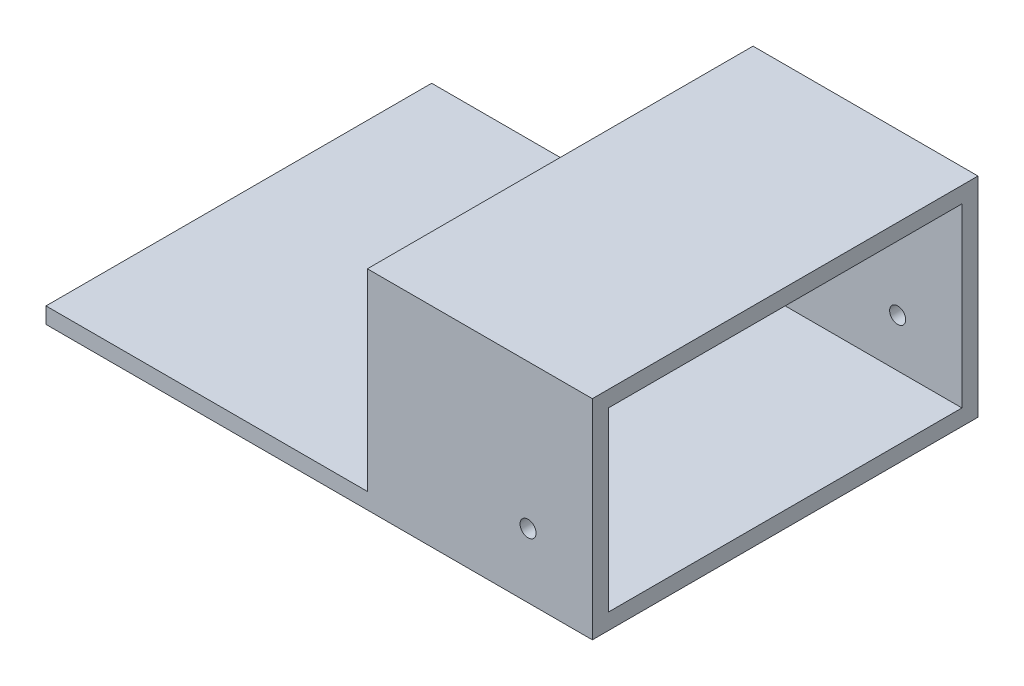
SolidWorks part; units mm, degrees
ref_plane "Front Plane" through (0, 0, 0) normal (0, 0, 1) x (1, 0, 0)
ref_plane "Top Plane" through (0, 0, 0) normal (0, 1, 0) x (1, 0, 0)
ref_plane "Right Plane" through (0, 0, 0) normal (1, 0, 0) x (0, 0, -1)
sketch "Sketch1" plane through (0, 0, 0) normal (0, 1, 0) x (1, 0, 0)
  line L0 (-215.9, 152.4) -> (-215.9, 0)
  line L1 (0, 0) -> (-88.9, 0)
  line L2 (0, 0) -> (0, 152.4)
  line L3 (0, 152.4) -> (-88.9, 152.4)
  line L4 (-88.9, 0) -> (-88.9, 152.4)
  line L5 (-88.9, 152.4) -> (-215.9, 152.4)
  line L15 (-215.9, 0) -> (0, 0)
  line L19 (-215.9, 152.4) -> (0, 152.4)
  dimension "D1" = 152.4
  dimension "D2" = 88.9
  dimension "D3" = 215.9
extrude "Boss-Extrude1" add sketch "Sketch1" along normal blind 6.35 contours L0 L15 L4 L5 region at (-152.4, 0, -76.2)
extrude "Boss-Extrude2" add sketch "Sketch1<7>" along normal blind 82.55 contours L4 L1 L2 L3 region at (-44.45, 0, -76.2)
sketch "Sketch1<7>" plane through (0, 0, 0) normal (0, 1, 0) x (1, 0, 0) same geometry as "Sketch1"
sketch "Sketch29" plane through (-88.9, 0, 0) normal (-1, 0, 0) x (0, 0, 1)
  line L0 (-152.4, 82.55) -> (-152.4, 6.35) construction
  line L1 (-146.05, 76.2) -> (-6.35, 76.2)
  line L2 (-146.05, 76.2) -> (-146.05, 6.35)
  line L3 (-146.05, 6.35) -> (-6.35, 6.35)
  line L4 (-6.35, 76.2) -> (-6.35, 6.35)
  line L5 (0, 82.55) -> (-152.4, 82.55) construction
  line L6 (-152.4, 6.35) -> (0, 6.35) construction
  line L7 (0, 82.55) -> (0, 6.35) construction
  dimension "D1" = 6.35
  dimension "D2" = 6.35
  dimension "D3" = 0
  dimension "D4" = 6.35
extrude "Cut-Extrude4" cut sketch "Sketch29" against normal through all
hole_wizard "1/4 (0.25) Diameter Hole2" positions "Sketch30" profile "Sketch31" hole size "1/4" standard "ANSI Inch" end condition through all
sketch "Sketch30" plane through (0, 0, -152.4) normal (0, 0, -1) x (-1, 0, 0)
  line L0 (0, 0) -> (215.9, 0) construction
  line L1 (0, 82.55) -> (0, 0) construction
  point P0 (25.4, 25.4)
  dimension "D1" = 25.4
  dimension "D2" = 25.4
sketch "Sketch31" plane through (-25.4, 25.4, -152.4) normal (1, 0, 0) x (0, 1, 0)
  line L0 (0, 0) -> (0, 152.4)
  line L1 (0, 152.4) -> (3.175, 152.4)
  line L2 (3.175, 152.4) -> (3.175, 0)
  line L5 (3.175, 0) -> (0, 0)
  line L11 (0, -6.35) -> (0, 107.95) construction
  dimension "Thru Hole Dia." = 6.35
  dimension "Thru Hole Depth" = 152.4
